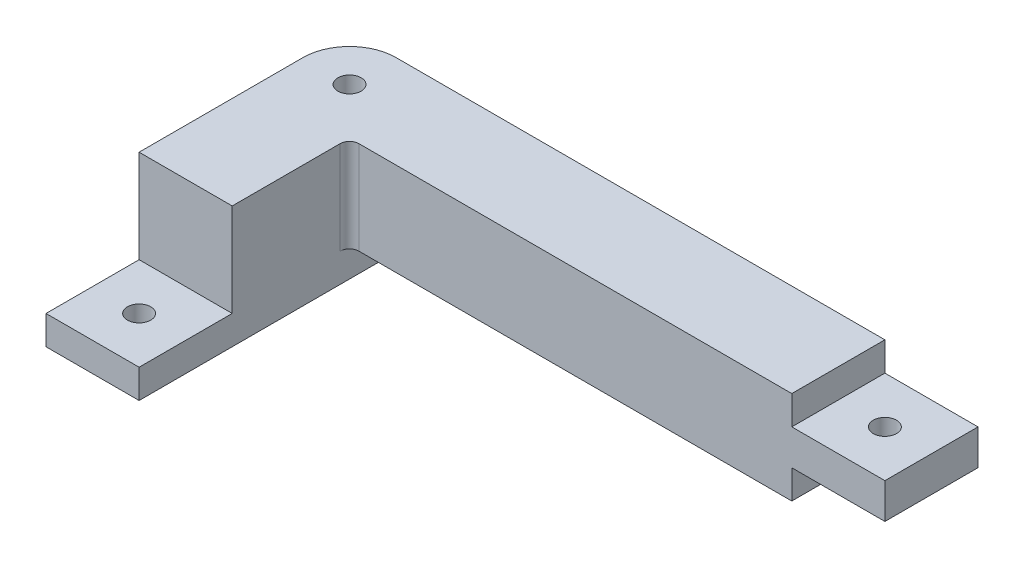
SolidWorks part; units mm, degrees
ref_plane "Front Plane" through (0, 0, 0) normal (0, 0, 1) x (1, 0, 0)
ref_plane "Top Plane" through (0, 0, 0) normal (0, 1, 0) x (1, 0, 0)
ref_plane "Right Plane" through (0, 0, 0) normal (1, 0, 0) x (0, 0, -1)
sketch "Sketch1" plane through (0, 0, 0) normal (0, 1, 0) x (1, 0, 0)
  line L1 (26.3502, -56.9444) -> (0.9502, -56.9444)
  line L2 (26.3502, -56.9444) -> (26.3502, 25.8596)
  line L3 (26.3502, 25.8596) -> (0.9502, 25.8596)
  line L4 (0.9502, -56.9444) -> (0.9502, 25.8596)
  dimension "D1" = 82.804
  dimension "D2" = 25.4
extrude "Boss-Extrude1" add sketch "Sketch1" along normal blind 33.274
sketch "Sketch3" plane through (26.3502, 0, 0) normal (1, 0, 0) x (0, 0, -1)
  line L1 (25.8596, 33.274) -> (0.4596, 33.274)
  line L2 (25.8596, 33.274) -> (25.8596, 7.874)
  line L3 (25.8596, 7.874) -> (0.4596, 7.874)
  line L4 (0.4596, 33.274) -> (0.4596, 7.874)
  dimension "D1" = 25.4
  dimension "D2" = 25.4
extrude "Boss-Extrude2" add sketch "Sketch3" along normal blind 120.65
sketch "Sketch4" plane through (0, 0, 56.9444) normal (0, 0, 1) x (1, 0, 0)
  line L0 (26.3502, 33.274) -> (26.3502, 0) construction
  line L4 (0.9502, 33.274) -> (26.3502, 33.274)
  line L5 (0.9502, 33.274) -> (0.9502, 7.874)
  line L6 (0.9502, 7.874) -> (26.3502, 7.874)
  line L7 (26.3502, 33.274) -> (26.3502, 7.874)
  dimension "D1" = 25.4
extrude "Cut-Extrude2" cut sketch "Sketch4" against normal blind 25.4
sketch "Sketch5" plane through (147.0002, 0, 0) normal (1, 0, 0) x (0, 0, -1)
  line L0 (0.4596, 15.748) -> (25.8596, 15.748)
  line L1 (0.4596, 33.274) -> (0.4596, 7.874) construction
  line L2 (25.8596, 7.874) -> (25.8596, 33.274) construction
  line L3 (0.4596, 25.4) -> (25.8596, 25.4)
  line L4 (25.8596, 33.274) -> (0.4596, 33.274) construction
  line L5 (0.4596, 25.4) -> (0.4596, 15.748)
  line L6 (25.8596, 25.4) -> (25.8596, 15.748)
  dimension "D1" = 7.874
  dimension "D2" = 9.652
extrude "Boss-Extrude3" add sketch "Sketch5" along normal blind 25.4
sketch "Sketch7" plane through (0, 25.4, 0) normal (0, 1, 0) x (1, 0, 0)
  line L0 (147.0002, 25.8596) -> (172.4002, 0.4596) construction
  circle A0 centre (159.7002, 13.1596) radius 3.175
  dimension "D1" = 6.35
extrude "Cut-Extrude4" cut sketch "Sketch7" against normal blind 41.402
sketch "Sketch8" plane through (0, 7.874, 0) normal (0, 1, 0) x (1, 0, 0)
  line L0 (0.9502, -31.5444) -> (26.3502, -56.9444) construction
  circle A0 centre (13.6502, -44.2444) radius 3.175
  dimension "D1" = 6.35
extrude "Cut-Extrude5" cut sketch "Sketch8" against normal blind 25.4
sketch "Sketch6" plane through (0, 33.274, 0) normal (0, 1, 0) x (1, 0, 0)
  line L1 (159.7002, 13.1596) -> (0.9502, 13.1596) construction
  line L3 (0.9502, 25.8596) -> (0.9502, -31.5444) construction
  line L4 (13.6502, -44.2444) -> (13.6502, 25.8596) construction
  line L5 (147.0002, 25.8596) -> (0.9502, 25.8596) construction
  circle A1 centre (13.6502, 13.1596) radius 3.175
  dimension "D1" = 6.35
extrude "Cut-Extrude3" cut sketch "Sketch6" against normal blind 41.402
fillet "Fillet1" radius 12.7 1 edges at (0.9502, 16.637, -25.8596)
fillet "Fillet2" radius 2.54 1 edges at (26.3502, 20.574, -0.4596)
